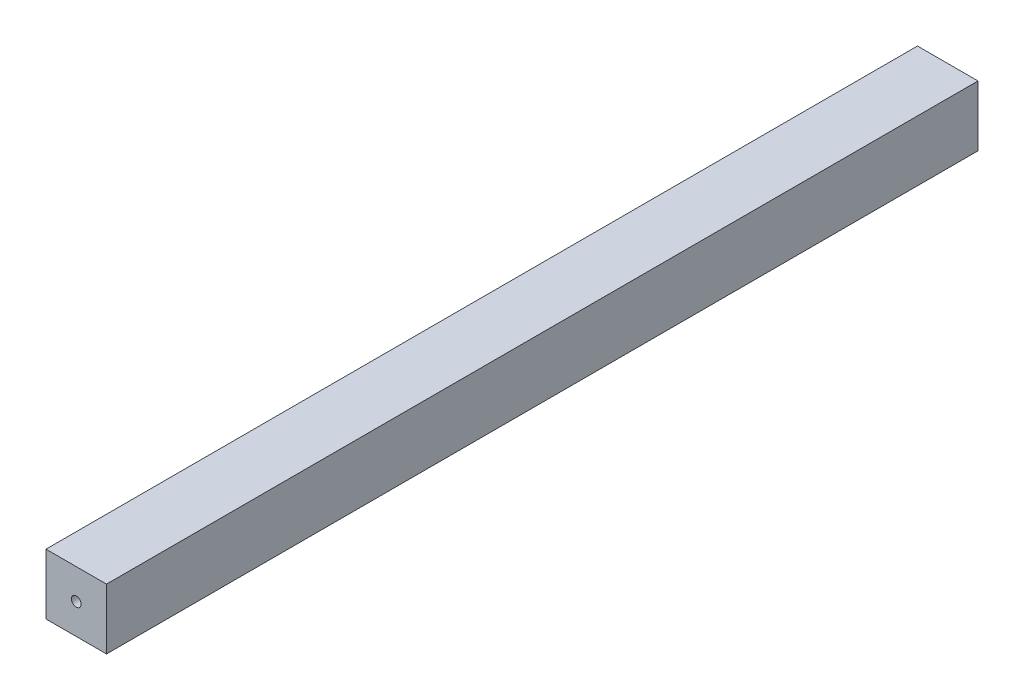
SolidWorks part; units mm, degrees
ref_plane "前视基准面" through (0, 0, 0) normal (0, 0, 1) x (1, 0, 0)
ref_plane "上视基准面" through (0, 0, 0) normal (0, 1, 0) x (1, 0, 0)
ref_plane "右视基准面" through (0, 0, 0) normal (1, 0, 0) x (0, 0, -1)
other "Configuration Table"
sketch "Sketch1" plane through (0, 0, 0) normal (0, 0, 1) x (1, 0, 0)
  line L1 (-25, -25) -> (25, -25)
  line L2 (-25, -25) -> (-25, 25)
  line L3 (-25, 25) -> (25, 25)
  line L4 (25, -25) -> (25, 25)
  line L5 (-25, -25) -> (25, 25) construction
  line L6 (-25, 25) -> (25, -25) construction
  point P0 (0, 0)
extrude "Boss-Extrude1" add sketch "Sketch1" along normal blind 720
ref_plane "Plane1" through (0, 0, 720) normal (0, 0, 1) x (1, 0, 0)
sketch "Sketch2" plane through (0, 0, 720) normal (0, 0, 1) x (1, 0, 0)
  circle A0 centre (0, 0) radius 4
extrude "Cut-Extrude1" cut sketch "Sketch2" against normal blind 30
ref_plane "top_face" through (0, 0, 720) normal (0, 0, 1) x (1, 0, 0)
sketch3d "3DSketch1"
  line L0 (0, 0, 720) -> (0, 0, 690) construction
ref_axis "leg_hole_axis" through (0, 0, 720) along (0, 0, -1)
sketch "Sketch3" plane through (0, 0, 0) normal (0, 0, 1) x (1, 0, 0)
  line L1 (-25, -25) -> (25, -25)
  line L2 (-25, -25) -> (-25, 25)
  line L3 (-25, 25) -> (25, 25)
  line L4 (25, -25) -> (25, 25)
  line L5 (-25, -25) -> (25, 25) construction
  line L6 (-25, 25) -> (25, -25) construction
  point P0 (0, 0)
extrude "Boss-Extrude2" add sketch "Sketch3" along normal blind 720
ref_plane "Plane3" through (0, 0, 720) normal (0, 0, 1) x (1, 0, 0)
sketch "Sketch4" plane through (0, 0, 720) normal (0, 0, 1) x (1, 0, 0)
  circle A0 centre (0, 0) radius 4
extrude "Cut-Extrude2" cut sketch "Sketch4" against normal blind 30
ref_plane "Plane4" through (0, 0, 720) normal (0, 0, 1) x (1, 0, 0)
sketch3d "3DSketch2"
  line L0 (0, 0, 720) -> (0, 0, 690) construction
ref_axis "Axis2" through (0, 0, 720) along (0, 0, -1)
